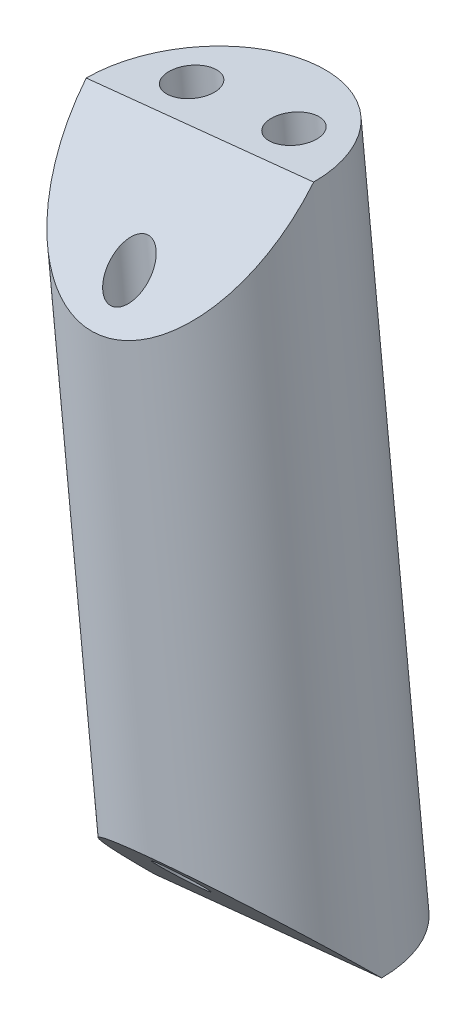
SolidWorks part; units mm, degrees
ref_plane "Front Plane" through (0, 0, 0) normal (0, 0, 1) x (1, 0, 0)
ref_plane "Top Plane" through (0, 0, 0) normal (0, 1, 0) x (1, 0, 0)
ref_plane "Right Plane" through (0, 0, 0) normal (1, 0, 0) x (0, 0, -1)
sketch "Sketch2" plane through (0, 0, 0) normal (0, 0, 1) x (1, 0, 0)
  line L0 (0, 0) -> (90, 0)
  line L1 (90, 0) -> (90, 120)
  line L2 (90, 120) -> (0, 120)
  line L3 (0, 120) -> (0, 0)
  line L4 (0, 120) -> (-10, 120)
  line L5 (-10, 120) -> (-10, 16.9491)
  line L6 (-10, 120) -> (57.5, 127)
  line L7 (57.5, 127) -> (90, 124)
  line L8 (90, 120) -> (99, 60)
  line L10 (90, 124) -> (90, 120)
  line L11 (5.9147, 0) -> (5.9147, -25)
  line L12 (5.9147, -25) -> (-4.0853, -25)
  line L13 (-4.0853, -29) -> (-4.0853, 0)
  line L14 (80, 0) -> (80, -25)
  line L15 (80, -25) -> (90, -25)
  line L16 (90, -29) -> (90, 0)
  line L17 (15.7927, 122.6748) -> (5.4776, 222.1414)
  line L18 (5.4776, 222.1414) -> (21.3923, 223.7918)
  line L19 (21.3923, 223.7918) -> (31.7073, 124.3252)
  line L20 (7.6492, 201.201) -> (23.5639, 202.8514)
  line L21 (10.9066, 169.7905) -> (26.8212, 171.441)
  line L22 (-10, 120) -> (-20.0396, 216.8108)
  line L23 (-20.0396, 216.8108) -> (-4.125, 218.4612)
  line L24 (-4.125, 218.4612) -> (5.9147, 121.6504)
  line L25 (-17.926, 196.4296) -> (-2.0114, 198.08)
  line L26 (-14.7556, 165.8578) -> (1.159, 167.5082)
  line L27 (57.5, 127) -> (46.9095, 229.1223)
  line L28 (46.9095, 229.1223) -> (30.9949, 227.4719)
  line L29 (30.9949, 227.4719) -> (41.5853, 125.3496)
  line L30 (33.2245, 205.9725) -> (49.1391, 207.6229)
  line L31 (36.5688, 173.7233) -> (52.4835, 175.3737)
  line L34 (90, 124) -> (99.1917, 223.5767)
  line L35 (99.1917, 223.5767) -> (83.2594, 225.0473)
  line L36 (83.2594, 225.0473) -> (74.0677, 125.4707)
  line L38 (81.3243, 204.0838) -> (97.2566, 202.6132)
  line L39 (78.4217, 172.6386) -> (94.354, 171.1679)
  line L40 (62.4078, 79.6749) -> (57.5, 127) construction
  line L41 (41.5853, 125.3496) -> (46.4931, 78.0244) construction
  line L42 (46.4931, 78.0244) -> (62.4078, 79.6749) construction
  line L43 (31.7073, 124.3252) -> (36.6151, 77.0001) construction
  line L44 (36.6151, 77.0001) -> (20.7005, 75.3496) construction
  line L45 (20.7005, 75.3496) -> (15.7927, 122.6748) construction
  line L46 (5.9147, 121.6504) -> (10.8224, 74.3253) construction
  line L47 (10.8224, 74.3253) -> (-5.0922, 72.6749) construction
  line L48 (-5.0922, 72.6749) -> (-10, 120) construction
  line L49 (74.0677, 125.4707) -> (69.6944, 78.0931) construction
  line L50 (69.6944, 78.0931) -> (85.7624, 78.0931) construction
  line L51 (85.7624, 78.0931) -> (90, 124) construction
  line L52 (-12.0823, 217.636) -> (10.4873, 0) construction
  line L53 (13.4349, 222.9666) -> (36.5574, 0) construction
  line L54 (38.9522, 228.2971) -> (62.6275, 0) construction
  line L55 (91.2256, 224.312) -> (70.5198, 0) construction
  line L59 (99, 60) -> (93.5277, 44.9649)
  line L60 (99, 60) -> (169.4769, 34.3485)
  line L61 (169.4769, 34.3485) -> (164.0046, 19.3134)
  line L62 (164.0046, 19.3134) -> (93.5277, 44.9649)
  line L63 (90, -2) -> (100, -2)
  line L64 (141.2862, 44.6091) -> (135.8138, 29.574)
  line L65 (99, 60) -> (55.7741, 75.7329) construction
  line L66 (55.7741, 75.7329) -> (50.3018, 60.6978) construction
  line L67 (100, -2) -> (100, -29)
  line L70 (-4.0853, -2) -> (-14.0853, -2)
  line L71 (-14.0853, -2) -> (-14.0853, -29)
  line L74 (-4.0853, 0) -> (0, 0)
  line L75 (-14.0853, -29) -> (-14.0853, -112.587)
  line L76 (-14.0853, -112.587) -> (100, -112.587)
  line L77 (100, -112.587) -> (100, -29)
  line L78 (-14.0853, -29) -> (100, -29)
  line L79 (-14.0853, -14.5) -> (100, -14.5) construction
  line L80 (31.7073, -112.587) -> (31.7073, -122.6232)
  line L81 (31.7073, -122.6232) -> (42.9573, -122.6232)
  line L82 (42.9573, -122.6232) -> (42.9573, -112.587)
  line L83 (-14.0853, -112.587) -> (-88.3667, -112.587)
  line L84 (-88.3667, -112.587) -> (-88.3667, -128.2699)
  line L85 (-88.3667, -128.2699) -> (169.4958, -128.2699)
  line L86 (169.4958, -128.2699) -> (169.4958, -112.587)
  line L87 (169.4958, -112.587) -> (100, -112.587)
  line L88 (90, 60) -> (-10, 60) construction
  line L89 (50.3018, 60.6978) -> (93.5277, 44.9649) construction
  line L90 (87.2806, 55.7521) -> (166.7408, 26.8309) construction
  line L91 (87.2806, 55.7521) -> (82.1749, 52.5336) construction
  line L92 (82.1749, 52.5336) -> (77.3257, 0) construction
  line L93 (83.1185, 56.6957) -> (86.337, 51.59) construction
  arc A0 (-10, 16.9491) -> (-4.0853, 0) centre (14.9876, 16.1624) ccw
  arc A1 (93.5277, 44.9649) -> (90, 0) centre (-126.4069, 39.5988) cw
  point P42 (41.1818, 206.7977)
  point P100 (84.7278, 54.1428)
  point P101 (84.7278, 54.1428)
  dimension "D11" = 47.3684
  dimension "D35" = 9
  dimension "D32" = 220
  dimension "D36" = 25
  dimension "D1" = 120
  dimension "D2" = 90
  dimension "D3" = 10
  dimension "D5" = 67.862
  dimension "D6" = 7
  dimension "D7" = 4
  dimension "D8" = 16
  dimension "D9" = 16
  dimension "D10" = 100
  dimension "D12" = 31.5789
  dimension "D13" = 16
  dimension "D14" = 16
  dimension "D15" = 16
  dimension "D16" = 25.7927
  dimension "D17" = 100
  dimension "D18" = 21.0526
  dimension "D19" = 31.5789
  dimension "D20" = 97.33
  dimension "D21" = 102.67
  dimension "D22" = 20.4905
  dimension "D23" = 30.7358
  dimension "D24" = 21.6147
  dimension "D25" = 32.4221
  dimension "D26" = 25
  dimension "D28" = 25
  dimension "D29" = 75
  dimension "D30" = 47.5789
  dimension "D31" = 30
  dimension "D33" = 46
  dimension "D34" = 20
  dimension "D37" = 2
  dimension "D38" = 2
  dimension "D39" = 27
  dimension "D40" = 10
  dimension "D41" = 10
  dimension "D42" = 27
  dimension "D43" = 14.5
  dimension "D44" = 127.5
ref_plane "Plane1" through (87.2806, 55.7521, 0) normal (-0.846, -0.5333, 0) x (0, 0, 1)
ref_plane "Plane2" through (82.1749, 52.5336, 0) normal (-0.0919, -0.9958, 0) x (-0.9958, 0.0919, 0)
ref_plane "Plane3" through (91.2256, 224.312, 0) normal (-0.0919, -0.9958, 0) x (-0.9958, 0.0919, 0)
ref_plane "Plane4" through (38.9522, 228.2971, 0) normal (0.1032, -0.9947, 0) x (-0.9947, -0.1032, 0)
ref_plane "Plane5" through (13.4349, 222.9666, 0) normal (0.1032, -0.9947, 0) x (-0.9947, -0.1032, 0)
ref_plane "Plane7" through (166.7408, 26.8309, 0) normal (0.9397, -0.342, 0) x (0, 0, -1)
ref_plane "Plane8" through (110.4217, -40.1902, 0) normal (0.9397, -0.342, 0) x (0, 0, -1)
ref_plane "Plane9" through (19.3664, 209.803, 0) normal (-0.0919, -0.9958, 0) x (-0.9958, 0.0919, 0)
ref_plane "Plane10" through (16.4638, 178.3578, 0) normal (-0.0919, -0.9958, 0) x (-0.9958, 0.0919, 0)
ref_plane "Plane11" through (-20.7793, 200.3721, 0) normal (0.1032, -0.9947, 0) x (-0.9947, -0.1032, 0)
ref_plane "Plane12" through (-17.435, 168.1229, 0) normal (0.1032, -0.9947, 0) x (-0.9947, -0.1032, 0)
ref_plane "Plane13" through (-20.5619, 198.2754, 0) normal (0.1032, -0.9947, 0) x (-0.9947, -0.1032, 0)
ref_plane "Plane14" through (-17.3045, 166.8649, 0) normal (0.1032, -0.9947, 0) x (-0.9947, -0.1032, 0)
ref_plane "Plane15" through (-12.0823, 217.636, 0) normal (0.1032, -0.9947, 0) x (-0.9947, -0.1032, 0)
ref_plane "Plane16" through (-20.3445, 196.1788, 0) normal (0.1032, -0.9947, 0) x (-0.9947, -0.1032, 0)
ref_plane "Plane17" through (-17.1741, 165.607, 0) normal (0.1032, -0.9947, 0) x (-0.9947, -0.1032, 0)
ref_plane "Plane18" through (12.1098, 131.1899, 0) normal (-0.0919, -0.9958, 0) x (-0.9958, 0.0919, 0)
ref_plane "Plane19" through (-12.4184, 119.7492, 0) normal (0.1032, -0.9947, 0) x (-0.9947, -0.1032, 0)
ref_plane "Plane20" through (0, 0, 0) normal (0, 0, 1) x (0.1032, -0.9947, 0)
ref_plane "Plane21" through (0, 0, 0) normal (0, 0, 1) x (-0.0919, -0.9958, 0)
ref_plane "Plane22" through (10.3758, 1.076, 0) normal (-0.9947, -0.1032, 0) x (0.1032, -0.9947, 0)
ref_plane "Plane23" through (36.1684, 3.7508, 0) normal (-0.9947, -0.1032, 0) x (0.1032, -0.9947, 0)
ref_plane "Plane24" through (61.9611, 6.4256, 0) normal (-0.9947, -0.1032, 0) x (0.1032, -0.9947, 0)
ref_plane "Plane25" through (69.924, -6.4545, 0) normal (-0.9958, 0.0919, 0) x (-0.0919, -0.9958, 0)
sketch "Sketch3" plane through (-20.3445, 196.1788, 0) normal (0.1032, -0.9947, 0) x (-0.9947, -0.1032, 0)
  line L0 (-2.4314, 0) -> (-18.4314, 0) construction
  circle A0 centre (-10.4314, 0) radius 8
  dimension "D1" = 16
extrude "Boss-Extrude1" add sketch "Sketch3" along normal blind 46.1037
sketch "Sketch4" plane through (10.3758, 1.076, 0) normal (-0.9947, -0.1032, 0) x (0.1032, -0.9947, 0)
  line L0 (-197.2309, 0) -> (-189.2309, 8)
  line L1 (-197.2309, 8) -> (-197.2309, -8) construction
  line L2 (-151.1272, 8) -> (-197.2309, 8) construction
  line L3 (-189.2309, 8) -> (-197.2309, 8)
  line L4 (-197.2309, 8) -> (-197.2309, 0)
  line L5 (-159.1272, 8) -> (-151.1272, 8)
  line L6 (-151.1272, 8) -> (-151.1272, 0)
  line L7 (-217.7214, 0) -> (1.0818, 0) construction
  line L8 (-151.1272, 0) -> (-159.1272, 8)
  dimension "D1" = 45
  dimension "D2" = 45
extrude "Cut-Extrude1" cut sketch "Sketch4" against normal through all and the other way through all
sketch "Sketch5" plane through (10.3758, 1.076, 0) normal (-0.9947, -0.1032, 0) x (0.1032, -0.9947, 0)
  line L0 (-151.1272, 0) -> (-155.1272, 4)
  line L1 (-151.1272, 0) -> (-159.1272, 8) construction
  line L2 (-155.1272, 4) -> (-147.1272, 4)
  line L3 (-147.1272, 4) -> (-147.1272, 0)
  line L4 (-213.7055, 0) -> (7.2742, 0) construction
  line L6 (-151.1272, 0) -> (-147.1272, 4) construction
  line L7 (-147.1272, 0) -> (-151.1272, -4)
  line L8 (-151.1272, -8) -> (-151.1272, 0) construction
  line L9 (-151.1272, 0) -> (-151.1272, -4)
  dimension "D1" = 4
  dimension "D2" = 45
sketch "Sketch7" plane through (10.3758, 1.076, 0) normal (-0.9947, -0.1032, 0) x (0.1032, -0.9947, 0)
  line L0 (-193.2309, 4) -> (-197.2309, 0)
  line L1 (-217.7214, 0) -> (1.0818, 0) construction
  line L4 (-197.2309, -4) -> (-197.2309, 0)
  line L5 (-193.2309, 4) -> (-193.2309, 0)
  arc A0 (-197.2309, -4) -> (-193.2309, 0) centre (-197.2309, 0) ccw
  dimension "D1" = 4
  dimension "D2" = 4
sketch "Sketch8" plane through (-20.3445, 196.1788, 0) normal (-0.1032, 0.9947, 0) x (0.9947, 0.1032, 0)
  line L0 (2.4314, 0) -> (18.4314, 0) construction
  circle A0 centre (10.4314, -5.5) radius 1.4
  circle A1 centre (6.8314, 3) radius 1.6
  circle A2 centre (14.0314, 3) radius 1.6
  point P9 (10.4314, 0)
  dimension "D1" = 3.2
  dimension "D2" = 3.2
  dimension "D3" = 2.8
  dimension "D4" = 3
  dimension "D5" = 5.5
  dimension "D6" = 3.6
  dimension "D7" = 3.6
  dimension "D8" = 3
extrude "Cut-Extrude3" cut sketch "Sketch8" against normal through all and the other way through all
sketch "Sketch9" plane through (-20.3445, 196.1788, 0) normal (-0.1032, 0.9947, 0) x (0.9947, 0.1032, 0)
  line L0 (4.5289, 5.4) -> (16.3339, 5.4)
  line L1 (-101.1265, 0) -> (155.3606, 0) construction
  arc A0 (18.4314, 0) -> (2.4314, 0) centre (10.4314, 0) ccw construction
  arc A1 (4.5289, 5.4) -> (16.3339, 5.4) centre (10.4314, 0) cw
  dimension "D1" = 5.4
